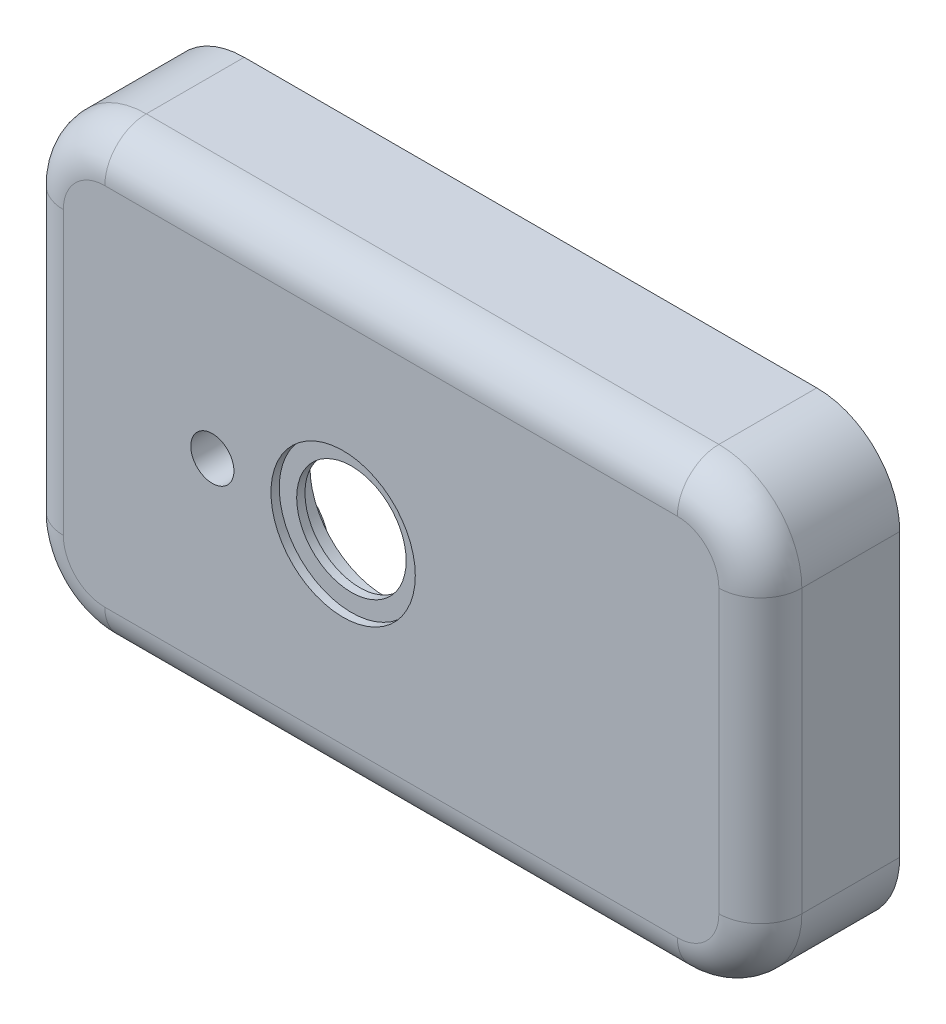
SolidWorks part; units mm, degrees
ref_plane "Front Plane" through (0, 0, 0) normal (0, 0, 1) x (1, 0, 0)
ref_plane "Top Plane" through (0, 0, 0) normal (0, 1, 0) x (1, 0, 0)
ref_plane "Right Plane" through (0, 0, 0) normal (1, 0, 0) x (0, 0, -1)
sketch "Sketch1" plane through (0, 0, 0) normal (0, 0, 1) x (1, 0, 0)
  line L0 (76.1986, 78.2029) -> (7.183, 78.2029) construction
  line L1 (-2.817, 68.2029) -> (-2.817, 55.8113) construction
  line L2 (-2.817, 55.8113) -> (2.183, 55.8113) construction
  line L3 (2.183, 55.8113) -> (2.183, 73.2029) construction
  line L4 (2.183, 73.2029) -> (81.1986, 73.2029) construction
  line L5 (81.1986, 73.2029) -> (81.1986, 55.2029) construction
  line L7 (86.1986, 55.2029) -> (86.1986, 68.2029) construction
  line L8 (7.183, 24.2029) -> (76.1986, 24.2029) construction
  line L9 (86.1986, 34.2029) -> (86.1986, 47.2029) construction
  line L11 (81.1986, 47.2029) -> (81.1986, 29.2029) construction
  line L12 (81.1986, 29.2029) -> (2.183, 29.2029) construction
  line L13 (2.183, 29.2029) -> (2.183, 46.6113) construction
  line L14 (2.183, 46.6113) -> (-2.817, 46.6113) construction
  line L15 (-2.817, 46.6113) -> (-2.817, 34.2029) construction
  line L16 (76.1986, 78.2029) -> (7.183, 78.2029)
  line L17 (-2.817, 68.2029) -> (-2.817, 55.8113)
  line L18 (-2.817, 55.8113) -> (2.183, 55.8113)
  line L19 (2.183, 55.8113) -> (2.183, 73.2029)
  line L20 (2.183, 73.2029) -> (81.1986, 73.2029)
  line L21 (81.1986, 73.2029) -> (81.1986, 55.2029)
  line L23 (86.1986, 55.2029) -> (86.1986, 68.2029)
  line L24 (7.183, 24.2029) -> (76.1986, 24.2029)
  line L25 (86.1986, 34.2029) -> (86.1986, 47.2029)
  line L27 (81.1986, 47.2029) -> (81.1986, 29.2029)
  line L28 (81.1986, 29.2029) -> (2.183, 29.2029)
  line L29 (2.183, 29.2029) -> (2.183, 46.6113)
  line L30 (2.183, 46.6113) -> (-2.817, 46.6113)
  line L31 (-2.817, 46.6113) -> (-2.817, 34.2029)
  line L32 (81.1986, 47.2029) -> (86.1986, 47.2029)
  line L33 (81.1986, 55.2029) -> (86.1986, 55.2029)
  arc A0 (7.183, 78.2029) -> (-2.817, 68.2029) centre (7.183, 68.2029) ccw construction
  arc A1 (86.1986, 68.2029) -> (76.1986, 78.2029) centre (76.1986, 68.2029) ccw construction
  arc A2 (76.1986, 24.2029) -> (86.1986, 34.2029) centre (76.1986, 34.2029) ccw construction
  arc A3 (-2.817, 34.2029) -> (7.183, 24.2029) centre (7.183, 34.2029) ccw construction
  arc A4 (7.183, 78.2029) -> (-2.817, 68.2029) centre (7.183, 68.2029) ccw
  arc A5 (86.1986, 68.2029) -> (76.1986, 78.2029) centre (76.1986, 68.2029) ccw
  arc A6 (76.1986, 24.2029) -> (86.1986, 34.2029) centre (76.1986, 34.2029) ccw
  arc A7 (-2.817, 34.2029) -> (7.183, 24.2029) centre (7.183, 34.2029) ccw
extrude "Boss-Extrude1" add sketch "Sketch1" along normal up to surface (14.8 mm away)
sketch "Sketch2" plane through (-2.817, 0, 0) normal (-1, 0, 0) x (0, 0, 1)
  line L0 (0, 55.8113) -> (0, 46.6113)
  line L2 (14.8, 55.8113) -> (0, 55.8113)
  line L3 (14.8, 55.8113) -> (14.8, 46.6113)
  line L4 (14.8, 46.6113) -> (0, 46.6113)
  line L5 (0, 55.8113) -> (0, 46.6113)
  arc A0 (0, 46.6113) -> (0, 55.8113) centre (0, 51.2113) ccw
  line M8 (0, 55.8113) -> (14.8, 55.8113)
extrude "Boss-Extrude2" add sketch "Sketch2" against normal up to surface (5 mm away) contours A0 L4 L3 M8 region at (-2.817, 51.2113, 9.1593) up to face at (2.183, 37.9071, 7.4)
sketch "Sketch3" plane through (0, 47.2029, 0) normal (0, 1, 0) x (1, 0, 0)
  line L4 (81.1986, -14.8) -> (86.1986, -14.8)
  line L5 (86.1986, -14.8) -> (86.1986, 0)
  line L6 (86.1986, 0) -> (81.1986, 0)
  line L7 (81.1986, 0) -> (81.1986, -14.8)
  line L8 (81.1986, -14.8) -> (86.1986, -14.8)
  line L9 (86.1986, -14.8) -> (86.1986, 0)
  line L10 (86.1986, 0) -> (81.1986, 0)
  line L11 (81.1986, 0) -> (81.1986, -14.8)
  dimension "D1" = 0
extrude "Boss-Extrude3" add sketch "Sketch3" along normal blind 12
sketch "Sketch4" plane through (0, 0, 14.8) normal (0, 0, 1) x (1, 0, 0)
  line L4 (86.1986, 34.2029) -> (86.1986, 68.2029)
  line L5 (76.1986, 78.2029) -> (7.183, 78.2029)
  line L6 (-2.817, 68.2029) -> (-2.817, 34.2029)
  line L7 (7.183, 24.2029) -> (76.1986, 24.2029)
  line L8 (86.1986, 34.2029) -> (86.1986, 68.2029)
  line L9 (76.1986, 78.2029) -> (7.183, 78.2029)
  line L10 (-2.817, 68.2029) -> (-2.817, 34.2029)
  line L11 (7.183, 24.2029) -> (76.1986, 24.2029)
  arc A4 (76.1986, 24.2029) -> (86.1986, 34.2029) centre (76.1986, 34.2029) ccw
  arc A5 (86.1986, 68.2029) -> (76.1986, 78.2029) centre (76.1986, 68.2029) ccw
  arc A6 (7.183, 78.2029) -> (-2.817, 68.2029) centre (7.183, 68.2029) ccw
  arc A7 (-2.817, 34.2029) -> (7.183, 24.2029) centre (7.183, 34.2029) ccw
  arc A8 (76.1986, 24.2029) -> (86.1986, 34.2029) centre (76.1986, 34.2029) ccw
  arc A9 (86.1986, 68.2029) -> (76.1986, 78.2029) centre (76.1986, 68.2029) ccw
  arc A10 (7.183, 78.2029) -> (-2.817, 68.2029) centre (7.183, 68.2029) ccw
  arc A11 (-2.817, 34.2029) -> (7.183, 24.2029) centre (7.183, 34.2029) ccw
  dimension "D1" = 0
extrude "Boss-Extrude4" add sketch "Sketch4" along normal blind 2
sketch "Sketch6" plane through (0, 0, 14.8) normal (0, 0, -1) x (-1, 0, 0)
  line L0 (-2.183, 58.2029) -> (-2.183, 73.2029)
  line L3 (-80.1986, 42.8779) -> (-81.1986, 42.8779)
  line L4 (-81.1986, 42.8779) -> (-81.1986, 29.2029)
  line L5 (-81.1986, 59.5279) -> (-79.7924, 59.5279)
  line L6 (-80.1986, 59.5279) -> (-54.5986, 59.5279)
  line L7 (-54.5986, 59.5279) -> (-54.5986, 42.8779)
  line L8 (-54.5986, 42.8779) -> (-80.1986, 42.8779)
  line L9 (-80.1986, 59.5279) -> (-54.5986, 59.5279)
  line L10 (-54.5986, 59.5279) -> (-54.5986, 42.8779)
  line L11 (-54.5986, 42.8779) -> (-80.1986, 42.8779)
  line L13 (-2.183, 73.2029) -> (-81.1986, 73.2029)
  line L14 (-81.1986, 73.2029) -> (-81.1986, 29.2029)
  line L15 (-81.1986, 29.2029) -> (-2.183, 29.2029)
  line L16 (-2.183, 29.2029) -> (-2.183, 73.2029)
  line L17 (-2.183, 73.2029) -> (-81.1986, 73.2029)
  line L18 (-81.1986, 73.2029) -> (-81.1986, 59.5279)
  line L19 (-81.1986, 29.2029) -> (-2.183, 29.2029)
  line L20 (-2.183, 29.2029) -> (-2.183, 44.2029)
  line L21 (-2.183, 58.2029) -> (-16.183, 58.2029)
  line L23 (-16.183, 58.2029) -> (-2.183, 58.2029)
  line L24 (-16.183, 58.2029) -> (-16.183, 44.2029)
  line L25 (-16.183, 44.2029) -> (-2.183, 44.2029)
  line L26 (-2.183, 58.2029) -> (-2.183, 44.2029)
  line M8 (-2.183, 73.2029) -> (-81.1986, 73.2029)
  line M9 (-81.1986, 73.2029) -> (-81.1986, 29.2029)
  line M10 (-81.1986, 29.2029) -> (-2.183, 29.2029)
  line M11 (-2.183, 29.2029) -> (-2.183, 73.2029)
  dimension "D1" = 1
  dimension "D2" = 0
extrude "Boss-Extrude5" add sketch "Sketch6" along normal blind 3 contours L25 L24 L21 L5 L9 L10 L11 L3 M11 M8 M9 M10 region at (39.8459, 51.2029, 14.8)
sketch "Sketch7" plane through (0, 0, 11.8) normal (0, 0, -1) x (-1, 0, 0)
  line L0 (-16.183, 51.2029) -> (-54.5986, 51.2029)
  line L1 (-16.183, 58.2029) -> (-16.183, 44.2029) construction
  line L2 (-54.5986, 59.5279) -> (-54.5986, 42.8779) construction
  circle A0 centre (-35.9072, 51.2029) radius 6.6
  circle A1 centre (-20.1434, 51.2029) radius 2.6
extrude "Cut-Extrude1" cut sketch "Sketch7" against normal blind 10 contours L0 A0 | L0 A0 | L0 A1 | L0 A1 region at (20.1434, 50.0994, 11.8) region at (20.1434, 52.3064, 11.8) region at (35.9072, 48.4018, 11.8) region at (35.9072, 54.004, 11.8)
fillet "Fillet1" radius 5 8 edges at (0.1119, 27.1318, 16.8) (-2.817, 51.2029, 16.8) (0.1119, 75.274, 16.8) (41.6908, 78.2029, 16.8) (83.2697, 75.274, 16.8) (86.1986, 51.2029, 16.8) (83.2697, 27.1318, 16.8) (41.6908, 24.2029, 16.8)
sketch "Sketch8" plane through (0, 0, 11.8) normal (0, 0, -1) x (-1, 0, 0)
  line L12 (-2.183, 44.2029) -> (-16.183, 44.2029)
  line L13 (-16.183, 44.2029) -> (-16.183, 58.2029)
  line L14 (-16.183, 58.2029) -> (-2.183, 58.2029)
  line L15 (-2.183, 58.2029) -> (-2.183, 73.2029)
  line L16 (-2.183, 73.2029) -> (-81.1986, 73.2029)
  line L17 (-81.1986, 73.2029) -> (-81.1986, 59.5279)
  line L18 (-81.1986, 59.5279) -> (-54.5986, 59.5279)
  line L19 (-54.5986, 59.5279) -> (-54.5986, 42.8779)
  line L20 (-54.5986, 42.8779) -> (-81.1986, 42.8779)
  line L21 (-81.1986, 42.8779) -> (-81.1986, 29.2029)
  line L22 (-81.1986, 29.2029) -> (-2.183, 29.2029)
  line L23 (-2.183, 29.2029) -> (-2.183, 44.2029)
  line L24 (-2.183, 44.2029) -> (-16.183, 44.2029)
  line L25 (-16.183, 44.2029) -> (-16.183, 58.2029)
  line L26 (-16.183, 58.2029) -> (-2.183, 58.2029)
  line L27 (-2.183, 58.2029) -> (-2.183, 73.2029)
  line L28 (-2.183, 73.2029) -> (-81.1986, 73.2029)
  line L29 (-81.1986, 73.2029) -> (-81.1986, 59.5279)
  line L30 (-81.1986, 59.5279) -> (-54.5986, 59.5279)
  line L31 (-54.5986, 59.5279) -> (-54.5986, 42.8779)
  line L32 (-54.5986, 42.8779) -> (-81.1986, 42.8779)
  line L33 (-81.1986, 42.8779) -> (-81.1986, 29.2029)
  line L34 (-81.1986, 29.2029) -> (-2.183, 29.2029)
  line L35 (-2.183, 29.2029) -> (-2.183, 44.2029)
  arc A0 (-73.0804, 29.2029) -> (-81.1986, 38.3083) centre (-77.1986, 33.7029) ccw construction
  circle A1 centre (-77.1986, 68.7029) radius 1.75 construction
  arc A2 (-81.1986, 64.0975) -> (-73.0804, 73.2029) centre (-77.1986, 68.7029) ccw construction
  circle A3 centre (-13.383, 33.7029) radius 1.75 construction
  arc A4 (-9.2648, 29.2029) -> (-17.5013, 29.2029) centre (-13.383, 33.7029) ccw construction
  arc A5 (-17.5013, 73.2029) -> (-9.2648, 73.2029) centre (-13.383, 68.7029) ccw construction
  arc A6 (-73.0804, 29.2029) -> (-81.1986, 38.3083) centre (-77.1986, 33.7029) ccw
  circle A7 centre (-77.1986, 68.7029) radius 1.75
  arc A8 (-81.1986, 64.0975) -> (-73.0804, 73.2029) centre (-77.1986, 68.7029) ccw
  circle A9 centre (-13.383, 33.7029) radius 1.75
  arc A10 (-9.2648, 29.2029) -> (-17.5013, 29.2029) centre (-13.383, 33.7029) ccw
  arc A11 (-17.5013, 73.2029) -> (-9.2648, 73.2029) centre (-13.383, 68.7029) ccw
  circle A12 centre (-13.383, 68.7029) radius 1.75 construction
  circle A13 centre (-13.383, 68.7029) radius 1.75
  circle A14 centre (-77.1986, 33.7029) radius 1.75 construction
  circle A15 centre (-77.1986, 33.7029) radius 1.75
  line M21 (-81.1986, 73.2029) -> (-81.1986, 59.5279)
  line M26 (-81.1986, 29.2029) -> (-2.183, 29.2029)
  dimension "D1" = 0
extrude "Boss-Extrude6" add sketch "Sketch8" along normal up to surface (11.8 mm away) separate body contours A6 L33 A15 M26 | A15 | A8 L28 A7 M21 | A7 | L28 A11 A13 | A13 | A10 A9 M26 | A9 region at (13.383, 29.3645, 11.8) region at (77.1395, 29.3493, 11.8) region at (13.383, 62.7645, 11.8) region at (72.7548, 64.7409, 11.8) region at (77.1986, 68.7029, 11.8) region at (13.383, 33.7029, 11.8) region at (13.383, 68.7029, 11.8) region at (77.1986, 33.7029, 11.8)
sketch "Sketch9" plane through (0, 0, 0) normal (0, 0, -1) x (-1, 0, 0)
  line L2 (-81.1986, 38.3083) -> (-81.1986, 29.2029)
  line L3 (-81.1986, 29.2029) -> (-73.0804, 29.2029)
  line L4 (-81.1986, 38.3083) -> (-81.1986, 29.2029)
  line L5 (-81.1986, 29.2029) -> (-73.0804, 29.2029)
  circle A0 centre (-13.383, 33.7029) radius 1.75 construction
  arc A1 (-73.0804, 29.2029) -> (-81.1986, 38.3083) centre (-77.1986, 33.7029) ccw
  circle A3 centre (-13.383, 68.7029) radius 1.75 construction
  circle A4 centre (-77.1986, 68.7029) radius 1.75 construction
  circle A5 centre (-77.1986, 33.7029) radius 1.75 construction
  circle A6 centre (-13.383, 33.7029) radius 1.75
  circle A7 centre (-13.383, 68.7029) radius 1.75
  circle A8 centre (-77.1986, 68.7029) radius 1.75
  circle A9 centre (-77.1986, 33.7029) radius 1.75
  dimension "D1" = 0
extrude "Cut-Extrude2" cut sketch "Sketch9" against normal blind 7 contours A8 | A9 | A7 | A6 region at (13.383, 68.7029, 0) region at (77.1986, 68.7029, 0) region at (77.1986, 33.7029, 0)
sketch "Sketch10" plane through (0, 0, 7) normal (0, 0, -1) x (-1, 0, 0)
  circle A0 centre (-13.383, 68.7029) radius 1.75 construction
  circle A1 centre (-13.383, 33.7029) radius 1.75 construction
  circle A2 centre (-77.1986, 68.7029) radius 1.75 construction
  circle A3 centre (-77.1986, 33.7029) radius 1.75 construction
  circle A4 centre (-13.383, 68.7029) radius 1.75 construction
  circle A5 centre (-13.383, 33.7029) radius 1.75 construction
  circle A6 centre (-77.1986, 68.7029) radius 1.75 construction
  circle A7 centre (-77.1986, 33.7029) radius 1.75 construction
  circle A8 centre (-77.1986, 68.7029) radius 2.75
  circle A9 centre (-77.1986, 33.7029) radius 2.75
  circle A10 centre (-13.383, 68.7029) radius 2.75
  circle A11 centre (-13.383, 33.7029) radius 2.75
extrude "Cut-Extrude3" cut sketch "Sketch10" against normal blind 3.5
ref_point "Point1"
ref_point "Point2"
ref_point "Point3"
ref_point "Point4"
ref_plane "Plane1" through (0, 33.7029, 0) normal (0, -1, 0) x (-1, 0, 0)
sketch "Sketch11" plane through (0, 33.7029, 0) normal (0, -1, 0) x (-1, 0, 0)
  line L0 (-75.4486, -7) -> (-75.4486, 0)
  line L1 (-78.9486, 0) -> (-78.9486, -7)
  line L2 (-78.9486, 0) -> (-78.9486, -7)
  line L3 (-75.4486, -7) -> (-75.4486, 0)
  line L4 (-11.633, -7) -> (-11.633, 0)
  line L5 (-15.133, 0) -> (-15.133, -7)
  line L6 (-15.133, 0) -> (-15.133, -7)
  line L7 (-11.633, -7) -> (-11.633, 0)
  line L8 (-10.633, -10.5) -> (-10.633, -7)
  line L9 (-16.133, -7) -> (-16.133, -10.5)
  line L10 (-16.133, -7) -> (-16.133, -10.5)
  line L11 (-10.633, -10.5) -> (-10.633, -7)
  line L12 (-74.4486, -10.5) -> (-74.4486, -7)
  line L13 (-79.9486, -7) -> (-79.9486, -10.5)
  line L14 (-79.9486, -7) -> (-79.9486, -10.5)
  line L15 (-74.4486, -10.5) -> (-74.4486, -7)
  line L16 (-74.4486, -7) -> (-75.4486, -7)
  line L17 (-78.9486, -7) -> (-79.9486, -7)
  line L18 (-74.4486, -10.5) -> (-79.9486, -10.5)
  line L19 (-75.4486, 0) -> (-78.9486, 0)
  line L20 (-10.633, -7) -> (-11.633, -7)
  line L21 (-15.133, -7) -> (-16.133, -7)
  line L22 (-10.633, -10.5) -> (-16.133, -10.5)
  line L23 (-11.633, 0) -> (-15.133, 0)
extrude "Cut-Extrude4" cut sketch "Sketch11" against normal blind 9.5
ref_plane "Plane2" through (0, 68.7029, 0) normal (0, -1, 0) x (-1, 0, 0)
sketch "Sketch12" plane through (0, 68.7029, 0) normal (0, -1, 0) x (-1, 0, 0)
  line L0 (-75.4486, -7) -> (-75.4486, 0)
  line L1 (-78.9486, 0) -> (-78.9486, -7)
  line L2 (-78.9486, 0) -> (-78.9486, -7)
  line L3 (-75.4486, -7) -> (-75.4486, 0)
  line L4 (-74.4486, -10.5) -> (-74.4486, -7)
  line L5 (-79.9486, -7) -> (-79.9486, -10.5)
  line L6 (-79.9486, -7) -> (-79.9486, -10.5)
  line L7 (-74.4486, -10.5) -> (-74.4486, -7)
  line L8 (-11.633, -7) -> (-11.633, 0)
  line L9 (-15.133, 0) -> (-15.133, -7)
  line L10 (-15.133, 0) -> (-15.133, -7)
  line L11 (-11.633, -7) -> (-11.633, 0)
  line L12 (-10.633, -10.5) -> (-10.633, -7)
  line L13 (-16.133, -7) -> (-16.133, -10.5)
  line L14 (-16.133, -7) -> (-16.133, -10.5)
  line L15 (-10.633, -10.5) -> (-10.633, -7)
  line L16 (-15.133, -7) -> (-16.133, -7)
  line L17 (-10.633, -7) -> (-11.633, -7)
  line L18 (-10.633, -10.5) -> (-16.133, -10.5)
  line L19 (-11.633, 0) -> (-15.133, 0)
  line L20 (-75.4486, 0) -> (-78.9486, 0)
  line L21 (-74.4486, -7) -> (-75.4486, -7)
  line L22 (-78.9486, -7) -> (-79.9486, -7)
  line L23 (-74.4486, -10.5) -> (-79.9486, -10.5)
extrude "Cut-Extrude5" cut sketch "Sketch12" along normal blind 9.5
sketch "Sketch13" plane through (2.183, 0, 0) normal (1, 0, 0) x (0, 0, -1)
  line L0 (-4.6, 51.2113) -> (-5.6, 51.2113)
  line L1 (-5.6, 51.2113) -> (-5.6, 44.2113)
  line L2 (-5.6, 51.2113) -> (-5.6, 58.2113)
  line L3 (-5.6, 44.2113) -> (-10.1, 44.2113)
  line L5 (-10.1, 44.2113) -> (-5.6, 44.2113)
  line L6 (-10.1, 44.2113) -> (-10.1, 58.2113)
  line L7 (-10.1, 58.2113) -> (-5.6, 58.2113)
  line L8 (-5.6, 44.2113) -> (-5.6, 58.2113)
  arc A0 (0, 55.8113) -> (0, 46.6113) centre (0, 51.2113) ccw construction
extrude "Cut-Extrude6" cut sketch "Sketch13" against normal blind 2 contours L7 L6 L3 L1 L2 region at (2.183, 51.2113, 7.85)
sketch "Sketch14" plane through (0, 0, 11.8) normal (0, 0, -1) x (-1, 0, 0)
  circle A0 centre (-35.9072, 51.2029) radius 6.6 construction
  circle A1 centre (-35.9072, 51.2029) radius 6.6 construction
  circle A2 centre (-35.9072, 51.2029) radius 9
extrude "Cut-Extrude7" cut sketch "Sketch14" against normal blind 3
sketch "Sketch15" plane through (0, 0, 0) normal (0, 0, -1) x (-1, 0, 0)
  line L0 (-75.4486, 68.7029) -> (-75.4486, 62.8593) construction
  line L1 (-73.0804, 73.2029) -> (-81.1986, 73.2029) construction
  line L2 (-81.1986, 73.2029) -> (-81.1986, 64.0975) construction
  line L3 (-15.133, 33.7029) -> (-15.133, 39.5465)
  line L4 (-17.5013, 29.2029) -> (-9.2648, 29.2029)
  line L5 (-11.633, 39.5465) -> (-11.633, 33.7029)
  line L6 (-15.133, 33.7029) -> (-15.133, 39.5465)
  line L7 (-17.5013, 29.2029) -> (-9.2648, 29.2029)
  line L8 (-11.633, 39.5465) -> (-11.633, 33.7029)
  line L9 (-78.9486, 62.8593) -> (-78.9486, 68.7029) construction
  line L10 (-78.9486, 33.7029) -> (-78.9486, 39.5465) construction
  line L11 (-81.1986, 38.3083) -> (-81.1986, 29.2029) construction
  line L12 (-81.1986, 29.2029) -> (-73.0804, 29.2029) construction
  line L13 (-75.4486, 39.5465) -> (-75.4486, 33.7029) construction
  line L14 (-11.633, 68.7029) -> (-11.633, 62.8593) construction
  line L15 (-9.2648, 73.2029) -> (-17.5013, 73.2029) construction
  line L16 (-15.133, 62.8593) -> (-15.133, 68.7029) construction
  line L17 (-75.4486, 68.7029) -> (-75.4486, 62.8593)
  line L18 (-73.0804, 73.2029) -> (-81.1986, 73.2029)
  line L19 (-81.1986, 73.2029) -> (-81.1986, 64.0975)
  line L20 (-78.9486, 62.8593) -> (-78.9486, 68.7029)
  line L21 (-78.9486, 33.7029) -> (-78.9486, 39.5465)
  line L22 (-81.1986, 38.3083) -> (-81.1986, 29.2029)
  line L23 (-81.1986, 29.2029) -> (-73.0804, 29.2029)
  line L24 (-75.4486, 39.5465) -> (-75.4486, 33.7029)
  line L25 (-11.633, 68.7029) -> (-11.633, 62.8593)
  line L26 (-9.2648, 73.2029) -> (-17.5013, 73.2029)
  line L27 (-15.133, 62.8593) -> (-15.133, 68.7029)
  arc A0 (-75.4486, 62.8593) -> (-73.0804, 73.2029) centre (-77.1986, 68.7029) ccw construction
  arc A1 (-81.1986, 64.0975) -> (-78.9486, 62.8593) centre (-77.1986, 68.7029) ccw construction
  arc A2 (-75.4486, 68.7029) -> (-78.9486, 68.7029) centre (-77.1986, 68.7029) ccw construction
  arc A3 (-15.133, 33.7029) -> (-11.633, 33.7029) centre (-13.383, 33.7029) ccw
  arc A4 (-15.133, 39.5465) -> (-17.5013, 29.2029) centre (-13.383, 33.7029) ccw
  arc A5 (-9.2648, 29.2029) -> (-11.633, 39.5465) centre (-13.383, 33.7029) ccw
  arc A6 (-15.133, 33.7029) -> (-11.633, 33.7029) centre (-13.383, 33.7029) ccw
  arc A7 (-15.133, 39.5465) -> (-17.5013, 29.2029) centre (-13.383, 33.7029) ccw
  arc A8 (-9.2648, 29.2029) -> (-11.633, 39.5465) centre (-13.383, 33.7029) ccw
  arc A9 (-78.9486, 33.7029) -> (-75.4486, 33.7029) centre (-77.1986, 33.7029) ccw construction
  arc A10 (-78.9486, 39.5465) -> (-81.1986, 38.3083) centre (-77.1986, 33.7029) ccw construction
  arc A11 (-73.0804, 29.2029) -> (-75.4486, 39.5465) centre (-77.1986, 33.7029) ccw construction
  arc A12 (-11.633, 62.8593) -> (-9.2648, 73.2029) centre (-13.383, 68.7029) ccw construction
  arc A13 (-17.5013, 73.2029) -> (-15.133, 62.8593) centre (-13.383, 68.7029) ccw construction
  arc A14 (-11.633, 68.7029) -> (-15.133, 68.7029) centre (-13.383, 68.7029) ccw construction
  arc A15 (-75.4486, 62.8593) -> (-73.0804, 73.2029) centre (-77.1986, 68.7029) ccw
  arc A16 (-81.1986, 64.0975) -> (-78.9486, 62.8593) centre (-77.1986, 68.7029) ccw
  arc A17 (-75.4486, 68.7029) -> (-78.9486, 68.7029) centre (-77.1986, 68.7029) ccw
  arc A18 (-78.9486, 33.7029) -> (-75.4486, 33.7029) centre (-77.1986, 33.7029) ccw
  arc A19 (-78.9486, 39.5465) -> (-81.1986, 38.3083) centre (-77.1986, 33.7029) ccw
  arc A20 (-73.0804, 29.2029) -> (-75.4486, 39.5465) centre (-77.1986, 33.7029) ccw
  arc A21 (-11.633, 62.8593) -> (-9.2648, 73.2029) centre (-13.383, 68.7029) ccw
  arc A22 (-17.5013, 73.2029) -> (-15.133, 62.8593) centre (-13.383, 68.7029) ccw
  arc A23 (-11.633, 68.7029) -> (-15.133, 68.7029) centre (-13.383, 68.7029) ccw
  dimension "D1" = 0
extrude "Cut-Extrude8" cut sketch "Sketch15" against normal blind 2
chamfer "Chamfer1" distance 5 distance2 1 2 edges at (10.633, 39.1479, 8.75) (16.133, 39.1479, 8.75) first distance on face at (10.633, 36.4254, 8.75) first distance on face at (16.133, 36.4254, 8.75)
chamfer "Chamfer2" distance 5 distance2 1 2 edges at (74.4486, 39.1479, 8.75) (79.9486, 39.1479, 8.75) first distance on face at (74.4486, 36.4254, 8.75) first distance on face at (79.9486, 36.4254, 8.75)
chamfer "Chamfer3" distance 1 distance2 5 2 edges at (79.9486, 63.2579, 8.75) (74.4486, 63.2579, 8.75) first distance on face at (76.5589, 64.4629, 6.7167)
chamfer "Chamfer4" distance 1 distance2 5 2 edges at (10.633, 63.2579, 8.75) (16.133, 63.2579, 8.75) first distance on face at (13.383, 65.3835, 6.7167)
sketch "Sketch16" plane through (0, 0, 11.8) normal (0, 0, -1) x (-1, 0, 0)
  line L0 (-77.1986, 62.6029) -> (49922.8014, 62.6029) construction
  line L1 (-77.1986, 39.8029) -> (49922.8014, 39.8029) construction
  line L2 (-49.925, 62.6029) -> (-49.925, -49937.3971) construction
  line L3 (-81.1986, 73.2029) -> (-81.1986, 59.5279) construction
  line L4 (-81.1986, 62.6029) -> (-49.925, 62.6029)
  line L5 (-81.1986, 62.6029) -> (-81.1986, 39.8029)
  line L6 (-81.1986, 39.8029) -> (-49.925, 39.8029)
  line L7 (-49.925, 62.6029) -> (-49.925, 39.8029)
extrude "Cut-Extrude9" cut sketch "Sketch16" against normal blind 4
sketch "Sketch17" plane through (0, 0, 16.8) normal (0, 0, 1) x (1, 0, 0)
  circle A0 centre (35.9072, 51.2029) radius 8.7
extrude "Cut-Extrude10" cut sketch "Sketch17" against normal blind 1
